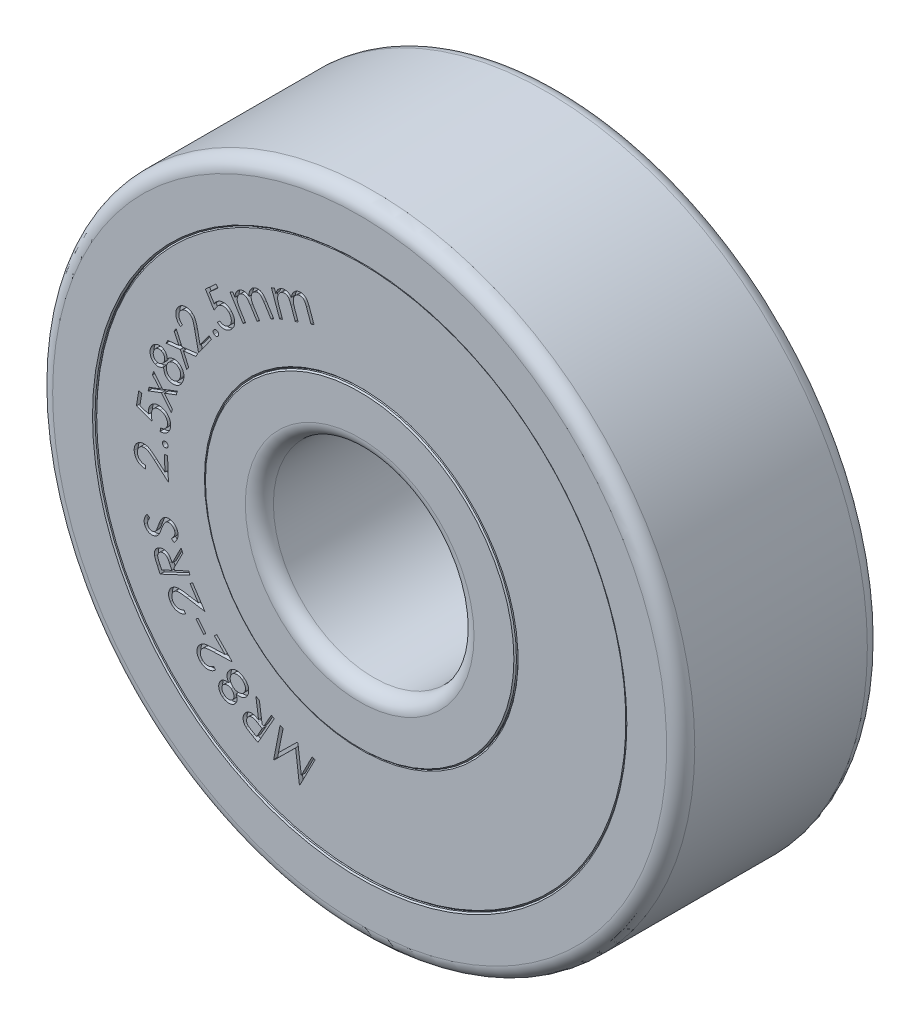
SolidWorks part; units mm, degrees
material "AISI 316 Annealed Stainless Steel Bar (SS)"
ref_plane "Front" through (0, 0, 0) normal (0, 0, 1) x (1, 0, 0)
ref_plane "Top" through (0, 0, 0) normal (0, 1, 0) x (1, 0, 0)
ref_plane "Right" through (0, 0, 0) normal (1, 0, 0) x (0, 0, -1)
sketch "LAYOUT R" plane through (0, 0, 0) normal (1, 0, 0) x (0, 0, -1)
  line L0 (-1.25, 1.25) -> (1.25, 1.25)
  line L1 (1.25, -4) -> (-1.25, -4) construction
  line L2 (1.25, -4) -> (1.25, 4) construction
  line L3 (1.25, 4) -> (-1.25, 4)
  line L4 (-1.25, -4) -> (-1.25, 4) construction
  line L5 (1.25, -4) -> (-1.25, 4) construction
  line L6 (1.25, 4) -> (-1.25, -4) construction
  line L7 (-1.25, 1.9375) -> (1.25, 1.9375)
  line L8 (-1.25, 3.3125) -> (1.25, 3.3125)
  line L11 (-17.5, 0) -> (17.5, 0) construction
  line L12 (-1.25, 4) -> (-1.25, 3.3125)
  line L13 (1.25, 4) -> (1.25, 3.3125)
  line L14 (-1.25, 3.3125) -> (-1.25, 1.9375)
  line L15 (1.25, 3.3125) -> (1.25, 1.9375)
  line L16 (-1.25, 1.9375) -> (-1.25, 1.25)
  line L17 (1.25, 1.9375) -> (1.25, 1.25)
  line L18 (-1.23, 3.3125) -> (-1.23, 1.9375)
  line L19 (1.23, 3.3125) -> (1.23, 1.9375)
  point P0 (0, 0)
  point P15 (0, 0)
  dimension "D1" = 2.5
  dimension "D2" = 8
  dimension "D3" = 1.25
  dimension "D6" = 0.02
  dimension "D7" = 0.02
  dimension "D4" = 1.9375
  dimension "D5" = 3.3125
sketch "Sketch R, INNER BODY" plane through (0, 0, 0) normal (1, 0, 0) x (0, 0, -1)
  line L0 (-1.25, 1.25) -> (1.25, 1.25) construction
  line L2 (-1.25, 1.9375) -> (1.25, 1.9375) construction
  line L4 (-1.25, 1.25) -> (1.25, 1.25)
  line L6 (-1.25, 1.9375) -> (1.25, 1.9375)
  line L8 (1.25, 1.9375) -> (1.25, 1.25) construction
  line L9 (-1.25, 1.9375) -> (-1.25, 1.25) construction
  line L10 (1.25, 1.9375) -> (1.25, 1.25)
  line L11 (-1.25, 1.9375) -> (-1.25, 1.25)
  line L12 (-17.5, 0) -> (17.5, 0) construction
  line L13 (-17.5, 0) -> (17.5, 0) construction
sketch "Sketch R, OUTER BODY" plane through (0, 0, 0) normal (1, 0, 0) x (0, 0, -1)
  line L2 (-1.25, 3.3125) -> (1.25, 3.3125) construction
  line L3 (1.25, 4) -> (-1.25, 4) construction
  line L6 (-1.25, 3.3125) -> (1.25, 3.3125)
  line L7 (1.25, 4) -> (-1.25, 4)
  line L8 (-17.5, 0) -> (17.5, 0) construction
  line L9 (-17.5, 0) -> (17.5, 0) construction
  line L10 (1.25, 4) -> (1.25, 3.3125) construction
  line L11 (-1.25, 4) -> (-1.25, 3.3125) construction
  line L12 (1.25, 4) -> (1.25, 3.3125)
  line L13 (-1.25, 4) -> (-1.25, 3.3125)
sketch "Sketch R, SEAL FACES" plane through (0, 0, 0) normal (1, 0, 0) x (0, 0, -1)
  line L0 (-17.5, 0) -> (17.5, 0) construction
  line L1 (-17.5, 0) -> (17.5, 0) construction
  line L3 (-1.25, 1.9375) -> (1.25, 1.9375) construction
  line L5 (-1.25, 3.3125) -> (1.25, 3.3125) construction
  line L7 (-1.23, 1.9375) -> (1.23, 1.9375)
  line L9 (-1.23, 3.3125) -> (1.23, 3.3125)
  line L10 (1.23, 3.3125) -> (1.23, 1.9375) construction
  line L11 (-1.23, 3.3125) -> (-1.23, 1.9375) construction
  line L12 (1.23, 3.3125) -> (1.23, 1.9375)
  line L13 (-1.23, 3.3125) -> (-1.23, 1.9375)
revolve "Revolve INNER BODY" add sketch "Sketch R, INNER BODY" angle 360 about L13
fillet "Fillet INNER BODY" radius 0.175 2 edges at (1.25, 0, 1.25) (1.25, 0, -1.25)
chamfer "Chamfer INNER BODY" distance 0.016 angle 45 2 edges at (1.9375, 0, -1.25) (1.9375, 0, 1.25)
revolve "Revolve OUTER BODY" add sketch "Sketch R, OUTER BODY" angle 360 about L9
fillet "Fillet OUTER BODY" radius 0.175 2 edges at (4, 0, -1.25) (4, 0, 1.25)
chamfer "Chamfer OUTER BODY" distance 0.016 angle 45 2 edges at (3.3125, 0, 1.25) (3.3125, 0, -1.25)
revolve "Revolve SEALS" add sketch "Sketch R, SEAL FACES" angle 360 about L1
chamfer "Chamfer SEALS" distance 0.016 angle 45 4 edges at (1.9375, 0, -1.23) (3.3125, 0, -1.23) (3.3125, 0, 1.23) (1.9375, 0, 1.23)
sketch "Sketch TEXT RADIUS 1 — MANUALLY ASSIGN TEXT AND FONT SIZE (FROM EQUATIONS)" plane through (0, 0, 1.23) normal (0, 0, 1) x (1, 0, 0)
  circle A0 centre (0, 0) radius 2.4188 construction
  text T0 "MR82-2RS  2.5x8x2.5mm" font "Century Gothic" height 0.4125
  dimension "D1" = 4.8375
extrude "Cut-Extrude SEAL LABEL 1" cut sketch "Sketch TEXT RADIUS 1 — MANUALLY ASSIGN TEXT AND FONT SIZE (FROM EQUATIONS)" against normal blind 0.05
sketch "Sketch TEXT RADIUS 2 — MANUALLY ASSIGN TEXT AND FONT SIZE (FROM EQUATIONS)" plane through (0, 0, -1.23) normal (0, 0, -1) x (-1, 0, 0)
  circle A0 centre (0, 0) radius 2.4188 construction
  text T0 "MR82-2RS  2.5x8x2.5mm" font "Century Gothic" height 0.4125
  dimension "D1" = 4.8375
extrude "Cut-Extrude SEAL LABEL 2" cut sketch "Sketch TEXT RADIUS 2 — MANUALLY ASSIGN TEXT AND FONT SIZE (FROM EQUATIONS)" against normal blind 0.05
equation "\"_i__BORE\"= 2.5"
equation "\"_i__OUTSIDE_DIAMETER\"= 8"
equation "\"_i__WIDTH\"= 2.5"
equation "\"_i_optional__TEXT_RADIUS_ADJUSTMENT\"= 0"
equation "\"_output__FONT_SIZE_mm\"= \"BODY_SPAN__SEAL__OF_RADIUS\" * \"param__FONT_SIZE_RATIO\"'MANUALLY ASSIGN TO FONT"
equation "\"BODY__HALF_WIDTH\"= \"_i__WIDTH\" / 2"
equation "\"BODY_SPAN___OF_DIAMETER\"= \"_i__OUTSIDE_DIAMETER\" - \"_i__BORE\""
equation "\"BODY_SPAN___OF_RADIUS\"= \"BODY_SPAN___OF_DIAMETER\" / 2"
equation "\"BODY_SPAN__BORE_AND_OD__OF RADIUS\"= ( \"BODY_SPAN___OF_RADIUS\" - \"BODY_SPAN__SEAL__OF_RADIUS\" ) / 2"
equation "\"BODY_SPAN__SEAL__OF_RADIUS\"= \"BODY_SPAN___OF_RADIUS\" * \"param__SEAL_PANEL_SPAN__RATIO_OF_BODY_RADIAN\""
equation "\"BORE__RADIUS\"= \"_i__BORE\" / 2"
equation "\"CORNER_RADII\"= \"_i__WIDTH\" * \"param__CORNER_RADII__ISO_MAX_RATIO_TO_WIDTH\""
equation "\"param__CORNER_RADII__ISO_MAX_RATIO_TO_WIDTH\"= 0.07'WHERE WIDTH IS LESS THAN DIAMETER"
equation "\"param__FONT_SIZE_RATIO\"= 0.3"
equation "\"param__SEAL_FACE_INSET__RATIO_OF_WIDTH\"= .01"
equation "\"param__SEAL_PANEL_SPAN__RATIO_OF_BODY_RADIAN\"= 0.5"
equation "\"param__SIDE_CHAMFERS__RATIO_TO_OD\"= 1 / 500"
equation "\"RING_INNER__OUTSIDE_RADIUS\"= \"BORE__RADIUS\" + \"BODY_SPAN__BORE_AND_OD__OF RADIUS\""
equation "\"RING_OUTER__OUTSIDE_RADIUS\"= ( \"_i__OUTSIDE_DIAMETER\" / 2 ) - \"BODY_SPAN__BORE_AND_OD__OF RADIUS\""
equation "\"SEAL_FACE_INSET\"= \"_i__WIDTH\" * \"param__SEAL_FACE_INSET__RATIO_OF_WIDTH\""
equation "\"SIDE_FACE_AND_SEAL_CHAMFERS\"= \"_i__OUTSIDE_DIAMETER\" * \"param__SIDE_CHAMFERS__RATIO_TO_OD\""
equation "\"TEXT_RADIUS\"= \"_i__BORE\" + ( \"BODY_SPAN___OF_DIAMETER\" / 2 ) - \"_output__FONT_SIZE_mm\" + \"_i_optional__TEXT_RADIUS_ADJUSTMENT\""
equation "\"D1@Chamfer INNER BODY\"=\"SIDE_FACE_AND_SEAL_CHAMFERS\""
equation "\"D1@Chamfer OUTER BODY\"=\"SIDE_FACE_AND_SEAL_CHAMFERS\""
equation "\"D1@Chamfer SEALS\"=\"SIDE_FACE_AND_SEAL_CHAMFERS\""
equation "\"D1@Fillet INNER BODY\"=\"CORNER_RADII\""
equation "\"D1@Fillet OUTER BODY\"=\"CORNER_RADII\""
equation "\"D1@LAYOUT R\"=\"_i__WIDTH\""
equation "\"D1@Sketch TEXT RADIUS 1 — MANUALLY ASSIGN TEXT AND FONT SIZE (FROM EQUATIONS)\" = \"TEXT_RADIUS\""
equation "\"D1@Sketch TEXT RADIUS 2 — MANUALLY ASSIGN TEXT AND FONT SIZE (FROM EQUATIONS)\" = \"TEXT_RADIUS\""
equation "\"D2@LAYOUT R\"=\"_i__OUTSIDE_DIAMETER\""
equation "\"D3@LAYOUT R\"=\"BORE__RADIUS\""
equation "\"D4@LAYOUT R\"=\"RING_INNER__OUTSIDE_RADIUS\""
equation "\"D5@LAYOUT R\"=\"RING_OUTER__OUTSIDE_RADIUS\""
